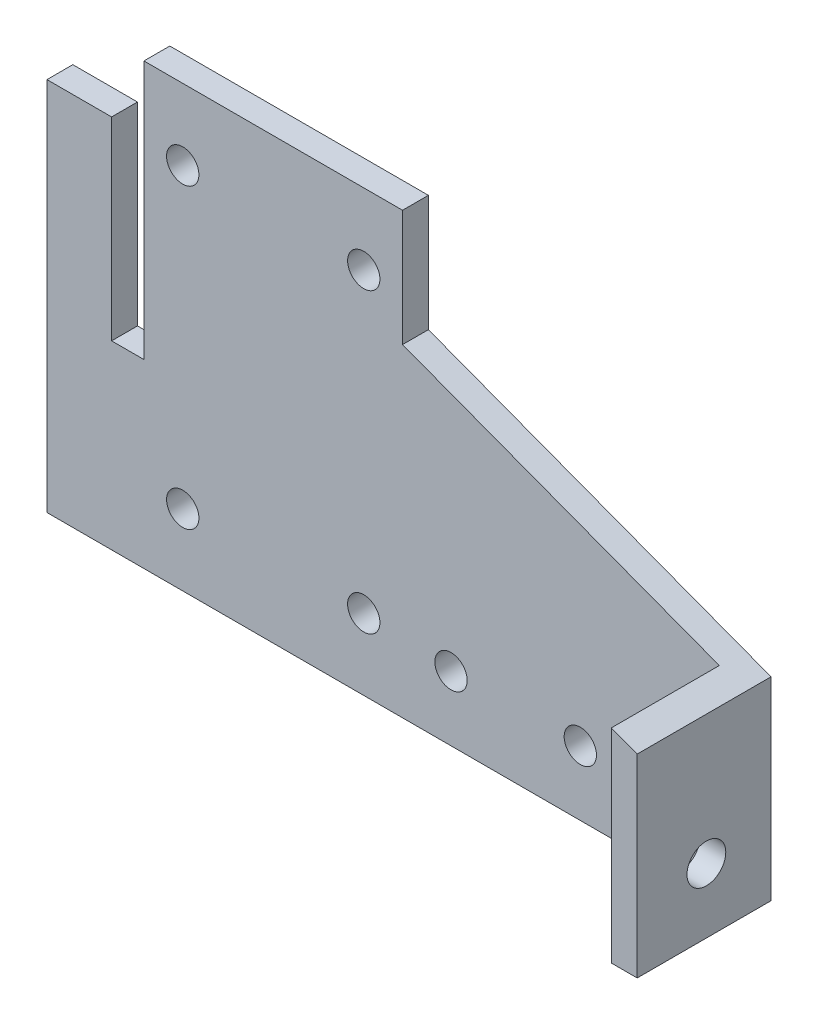
SolidWorks part; units mm, degrees
ref_plane "Спереди" through (0, 0, 0) normal (0, 0, 1) x (1, 0, 0)
ref_plane "Сверху" through (0, 0, 0) normal (0, 1, 0) x (1, 0, 0)
ref_plane "Справа" through (0, 0, 0) normal (1, 0, 0) x (0, 0, -1)
sketch "Эскиз1" plane through (0, 0, 0) normal (0, 0, 1) x (1, 0, 0)
  line L0 (35, 68) -> (35, 0) construction
  line L1 (0, 0) -> (108, 0)
  line L2 (0, 0) -> (0, 68)
  line L3 (0, 68) -> (55, 68)
  line L4 (108, 0) -> (108, 30)
  line L5 (21, 68) -> (21, 0) construction
  line L6 (55, 68) -> (55, 50)
  line L7 (97.0699, 10) -> (77.1265, 10) construction
  line L8 (49, 68) -> (49, 0) construction
  line L10 (108, 30) -> (55, 50)
  circle A0 centre (21, 57) radius 2.5
  circle A1 centre (49, 57) radius 2.5
  circle A2 centre (21, 11) radius 2.5
  circle A3 centre (49, 11) radius 2.5
  circle A4 centre (82.5, 10) radius 2.5
  circle A5 centre (62.5, 10) radius 2.5
  dimension "D8" = 5
  dimension "D9" = 5
  dimension "D10" = 5
  dimension "D11" = 5
  dimension "D18" = 5
  dimension "D20" = 20
  dimension "D1" = 108
  dimension "D2" = 68
  dimension "D3" = 55
  dimension "D4" = 30
  dimension "D5" = 35
  dimension "D6" = 14
  dimension "D7" = 14
  dimension "D12" = 46
  dimension "D13" = 46
  dimension "D14" = 11
  dimension "D15" = 11
  dimension "D16" = 20
  dimension "D17" = 10
  dimension "D19" = 25.5
extrude "Бобышка-Вытянуть1" add sketch "Эскиз1" along normal blind 4
sketch "Эскиз2" plane through (0, 0, 4) normal (0, 0, 1) x (1, 0, 0)
  line L1 (108, 0) -> (104, 0)
  line L2 (0, 0) -> (108, 0) construction
  line L3 (104, 0) -> (104, 31.5094)
  line L4 (108, 30) -> (55, 50) construction
  line L5 (104, 31.5094) -> (108, 30)
  line L6 (108, 30) -> (108, 0)
  dimension "D1" = 4
extrude "Бобышка-Вытянуть2" add sketch "Эскиз2" along normal blind 16.7
sketch "Эскиз3" plane through (108, 0, 0) normal (1, 0, 0) x (0, 0, -1)
  line L4 (0, 0) -> (0, 30) construction
  line L5 (-20.7, 0) -> (0, 0) construction
  circle A1 centre (-10, 10) radius 3
  dimension "D2" = 10
  dimension "D3" = 6
  dimension "D1" = 10
extrude "Вырез-Вытянуть1" cut sketch "Эскиз3" against normal blind 10
sketch "Эскиз4" plane through (0, 0, 4) normal (0, 0, 1) x (1, 0, 0)
  line L1 (0, 68) -> (15, 68)
  line L2 (0, 68) -> (0, 58)
  line L3 (0, 58) -> (10, 58)
  line L4 (15, 68) -> (15, 58)
  line L6 (15, 58) -> (15, 28)
  line L7 (15, 28) -> (10, 28)
  line L8 (10, 58) -> (10, 28)
  dimension "D1" = 15
  dimension "D2" = 10
  dimension "D3" = 40
  dimension "D4" = 5
extrude "Вырез-Вытянуть2" cut sketch "Эскиз4" against normal blind 10
